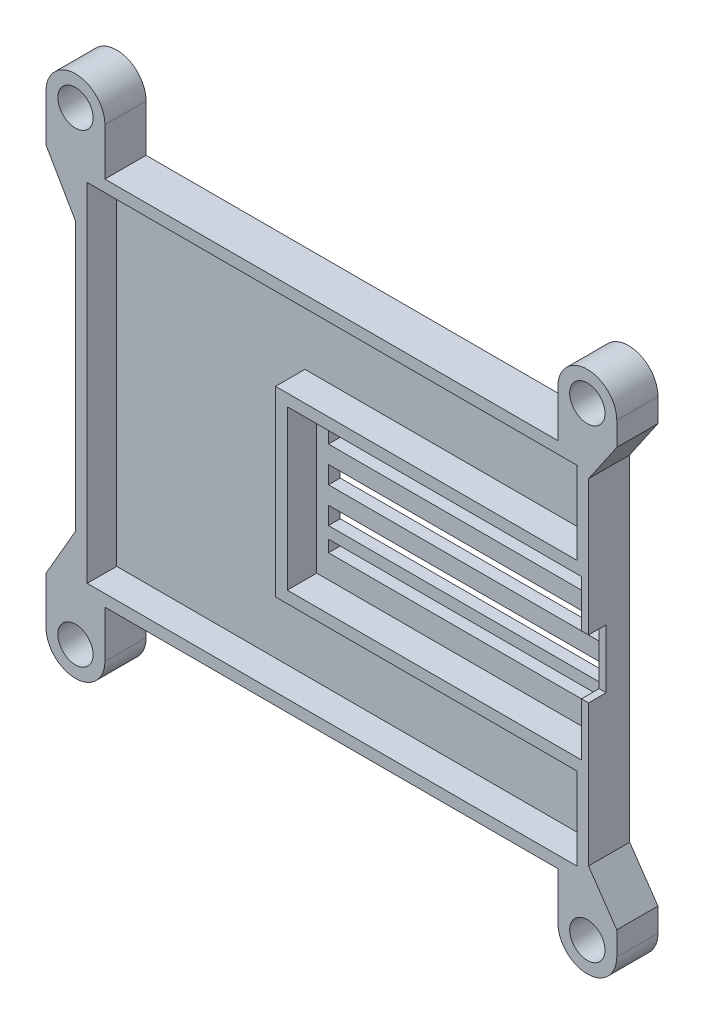
SolidWorks part; units mm, degrees
ref_plane "Front" through (0, 0, 0) normal (0, 0, 1) x (1, 0, 0)
ref_plane "Top" through (0, 0, 0) normal (0, 1, 0) x (1, 0, 0)
ref_plane "Right" through (0, 0, 0) normal (1, 0, 0) x (0, 0, -1)
sketch "草图1" plane through (0, 0, 0) normal (0, 0, 1) x (1, 0, 0)
  line L0 (0, 55.4124) -> (0, -66.1187) construction
  line L1 (-87.3866, 0) -> (75.5228, 0) construction
  line L2 (-46, 22.842) -> (-46, -22.842)
  line L3 (-46, -22.842) -> (-51, -31.5022)
  line L4 (-51, -31.5022) -> (-51, -39.5022)
  line L5 (-41, -39.5022) -> (-41, -31.5022)
  line L6 (-41, -31.5022) -> (36, -31.5022)
  line L7 (46, 39.5022) -> (46, -39.5022)
  line L8 (36, 39.5022) -> (36, 31.5022)
  line L9 (36, -31.5022) -> (36, -39.5022)
  line L10 (36, 31.5022) -> (-41, 31.5022)
  line L11 (-46, 22.842) -> (-51, 31.5022)
  line L12 (-51, 31.5022) -> (-51, 39.5022)
  line L13 (-41, 39.5022) -> (-41, 31.5022)
  line L19 (25, 13.5) -> (-25, -13.5) construction
  line L20 (25, -13.5) -> (-25, 13.5) construction
  arc A0 (-51, -39.5022) -> (-41, -39.5022) centre (-46, -39.5022) ccw
  arc A1 (36, -39.5022) -> (46, -39.5022) centre (41, -39.5022) ccw
  arc A2 (46, 39.5022) -> (36, 39.5022) centre (41, 39.5022) ccw
  arc A3 (-51, 39.5022) -> (-41, 39.5022) centre (-46, 39.5022) cw
  point P25 (0, 0)
  dimension "D3" = 5
  dimension "D5" = 5
  dimension "D9" = 5
  dimension "D12" = 5
  dimension "D2" = 92
  dimension "D4" = 8
  dimension "D6" = 8
  dimension "D7" = 30
  dimension "D8" = 5
  dimension "D10" = 8
  dimension "D11" = 63.0044
  dimension "D13" = 8
  dimension "D14" = 5
  dimension "D15" = 30
  dimension "D16" = 27
  dimension "D17" = 50
extrude "凸台-拉伸1" add sketch "草图1" along normal blind 2
sketch "草图3" plane through (0, 0, 2) normal (0, 0, 1) x (1, 0, 0)
  line L0 (46, -39.5022) -> (46, 39.5022) construction
  line L1 (40, 13.5) -> (-10, 13.5)
  line L2 (40, 13.5) -> (40, -13.5)
  line L3 (40, -13.5) -> (-10, -13.5)
  line L4 (-10, 13.5) -> (-10, -13.5)
  point P0 (0, 0)
  line M5 (-51, 31.5022) -> (-46, 22.842)
  line M6 (-46, 22.842) -> (-46, -22.842)
  line M7 (-46, -22.842) -> (-51, -31.5022)
  line M8 (-51, -31.5022) -> (-51, -39.5022)
  arc M9 (-51, -39.5022) -> (-41, -39.5022) centre (-46, -39.5022) ccw
  line M10 (-41, -39.5022) -> (-41, -31.5022)
  line M11 (-41, -31.5022) -> (36, -31.5022)
  line M12 (36, -31.5022) -> (36, -39.5022)
  arc M13 (36, -39.5022) -> (46, -39.5022) centre (41, -39.5022) ccw
  line M14 (46, -39.5022) -> (46, 39.5022)
  arc M15 (46, 39.5022) -> (36, 39.5022) centre (41, 39.5022) ccw
  line M16 (36, 39.5022) -> (36, 31.5022)
  line M17 (36, 31.5022) -> (-41, 31.5022)
  line M18 (-41, 31.5022) -> (-41, 39.5022)
  arc M19 (-41, 39.5022) -> (-51, 39.5022) centre (-46, 39.5022) ccw
  line M20 (-51, 39.5022) -> (-51, 31.5022)
  dimension "D1" = 27
  dimension "D2" = 50
  dimension "D3" = 6
extrude "凸台-拉伸2" add sketch "草图3" along normal blind 5 contours L4 L1 L2 L3 M20 M5 M6 M7 M8 M9 M10 M11 M12 M13 M14 M15 M16 M17 M18 M19 region at (-49.6835, 35.5022, 2)
sketch "草图5" plane through (0, 0, 7) normal (0, 0, 1) x (1, 0, 0)
  circle A0 centre (41, 39.5022) radius 3
  circle A1 centre (-46, 39.5022) radius 3
  circle A2 centre (41, -39.5022) radius 3
  circle A3 centre (-46, -39.5022) radius 3
  dimension "D1" = 6
  dimension "D2" = 6
  dimension "D3" = 6
  dimension "D4" = 6
extrude "切除-拉伸1" cut sketch "草图5" against normal blind 5
sketch "草图6" plane through (40, 0, 0) normal (-1, 0, 0) x (0, 0, 1)
  line L0 (7, -4.5) -> (7, 5.5)
  line L1 (7, -4.5) -> (4, -4.5)
  line L2 (7, 5.5) -> (4, 5.5)
  line L3 (4, -4.5) -> (4, 5.5)
  line L4 (7, 13.5) -> (7, -13.5) construction
  line L5 (7, 13.5) -> (2, 13.5) construction
  dimension "D1" = 3
  dimension "D2" = 10
  dimension "D3" = 18
extrude "切除-拉伸2" cut sketch "草图6" against normal through all
sketch "草图8" plane through (0, 0, 7) normal (0, 0, 1) x (1, 0, 0)
  line L0 (41.2, 28.5022) -> (46, 35.5022)
  line L1 (41.2, 28.5022) -> (41.2, -28.5022)
  line L2 (46, 5.5) -> (46, 39.5022) construction
  line L3 (41.2, -28.5022) -> (46, -35.5022)
  line L4 (46, -39.5022) -> (46, -4.5) construction
  circle A0 centre (41, 39.5022) radius 3 construction
  circle A2 centre (41, -39.5022) radius 3 construction
  dimension "D1" = 11
  dimension "D2" = 11
  dimension "D3" = 7
  dimension "D4" = 7
  dimension "D5" = 4.8
extrude "切除-拉伸5" cut sketch "草图8" against normal through all and the other way through all
sketch "草图9" plane through (0, 0, 7) normal (0, 0, 1) x (1, 0, 0)
  line L0 (39.2, 29.5022) -> (39.2, 15.5)
  line L1 (39.2, 29.5022) -> (-44, 29.5022)
  line L2 (39.2, 15.5) -> (-44, 15.5)
  line L3 (-44, 29.5022) -> (-44, 15.5)
  line L4 (39.2, -15.5) -> (39.2, -29.5022)
  line L5 (39.2, -15.5) -> (-44, -15.5)
  line L6 (39.2, -29.5022) -> (-44, -29.5022)
  line L7 (-44, -15.5) -> (-44, -29.5022)
  line L8 (-12, 15.5) -> (-44, 15.5)
  line L9 (-12, 15.5) -> (-12, -15.5)
  line L10 (-44, 15.5) -> (-44, -15.5)
  line L11 (-12, -15.5) -> (-44, -15.5)
  line L12 (41.2, 5.5) -> (41.2, 28.5022) construction
  line L13 (36, 31.5022) -> (-41, 31.5022) construction
  line L14 (40, 13.5) -> (-10, 13.5) construction
  line L15 (40, -13.5) -> (-10, -13.5) construction
  line L16 (-41, -31.5022) -> (36, -31.5022) construction
  line L17 (-46, 22.842) -> (-46, -22.842) construction
  line L18 (-10, 13.5) -> (-10, -13.5) construction
  dimension "D1" = 2
  dimension "D2" = 2
  dimension "D3" = 2
  dimension "D4" = 2
  dimension "D5" = 2
  dimension "D6" = 2
  dimension "D7" = 2
  dimension "D8" = 2
  dimension "D9" = 2
extrude "切除-拉伸6" cut sketch "草图9" against normal blind 5 contours L1 L3 L2 L0 | L5 L7 L6 L4 | L2 L10 L5 L9 region at (-2.4, 22.5011, 7) region at (-28, 0, 7) region at (-2.4, -22.5011, 7)
sketch "草图11" plane through (0, 0, 2) normal (0, 0, 1) x (1, 0, 0)
  line L0 (38, 9.5) -> (38, -9.5)
  line L1 (38, 9.5) -> (-8, 9.5)
  line L2 (38, -9.5) -> (-8, -9.5)
  line L3 (-8, 9.5) -> (-8, -9.5)
  line L4 (40, 13.5) -> (-10, 13.5) construction
  line L5 (40, -13.5) -> (-10, -13.5) construction
  line L6 (-10, 13.5) -> (-10, -13.5) construction
  line L7 (40, 13.5) -> (40, -13.5) construction
  line L8 (38, 6.5) -> (-8, 6.5)
  line L9 (38, 3.5) -> (-8, 3.5)
  line L10 (38, 0.5) -> (-8, 0.5)
  line L11 (38, -2.5) -> (-8, -2.5)
  line L12 (38, -5.5) -> (-8, -5.5)
  line L13 (38, -7.5) -> (-8, -7.5)
  dimension "D1" = 4
  dimension "D2" = 4
  dimension "D3" = 2
  dimension "D4" = 2
  dimension "D5" = 3
  dimension "D6" = 3
  dimension "D7" = 3
  dimension "D8" = 3
  dimension "D9" = 3
  dimension "D10" = 2
extrude "切除-拉伸8" cut sketch "草图11" against normal blind 10 contours L8 L0 L1 L3 | L10 L0 L9 L3 | L12 L0 L11 L3 | L0 L13 L3 L2 region at (15, 8, 2) region at (15, 2, 2) region at (15, -4, 2) region at (15, -8.5, 2)
sketch "草图14" plane through (0, 0, 2) normal (0, 0, 1) x (1, 0, 0)
  circle A0 centre (41, -39.5022) radius 2
  circle A1 centre (41, 39.5022) radius 2
  circle A2 centre (-46, 39.5022) radius 2
  circle A3 centre (-46, -39.5022) radius 2
  dimension "D1" = 4
  dimension "D2" = 4
  dimension "D3" = 4
  dimension "D4" = 4
extrude "切除-拉伸9" cut sketch "草图14" against normal blind 10
